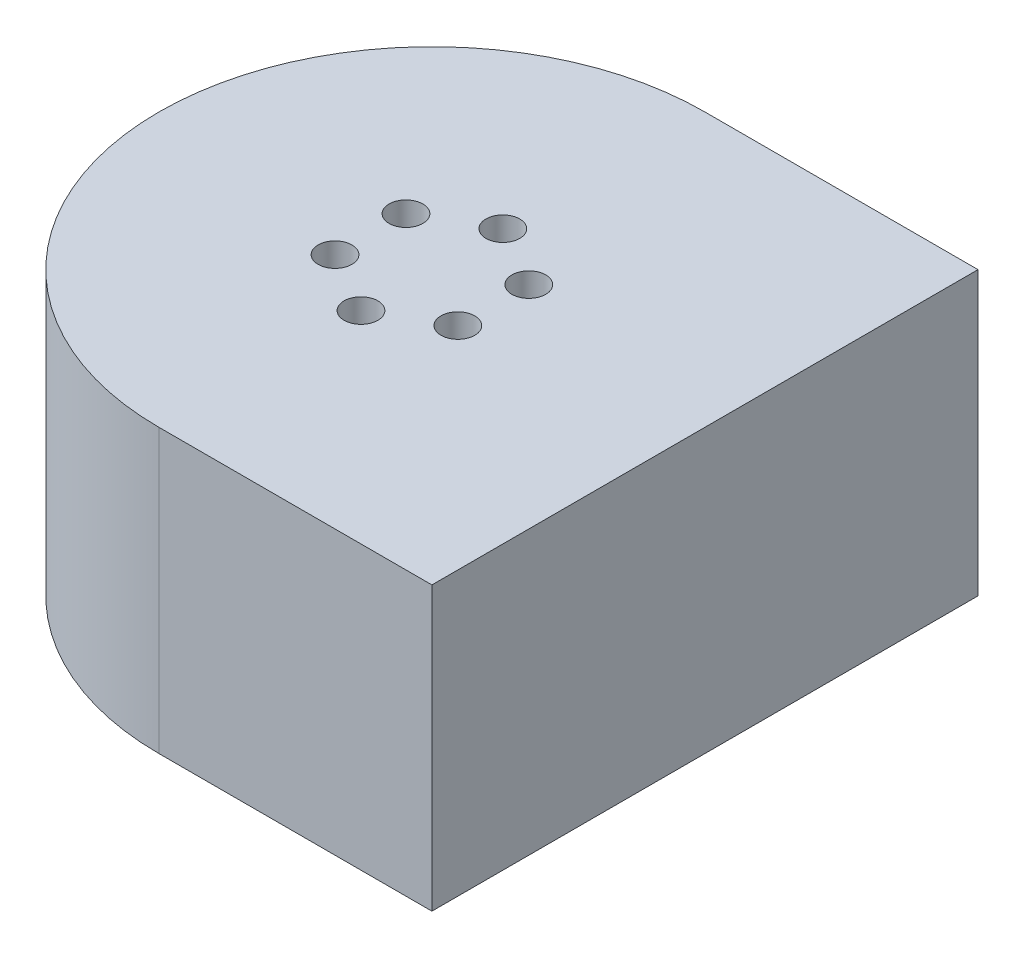
SolidWorks part; units mm, degrees
ref_plane "Front Plane" through (0, 0, 0) normal (0, 0, 1) x (1, 0, 0)
ref_plane "Top Plane" through (0, 0, 0) normal (0, 1, 0) x (1, 0, 0)
ref_plane "Right Plane" through (0, 0, 0) normal (1, 0, 0) x (0, 0, -1)
sketch "Sketch1" plane through (0, 0, 0) normal (0, 1, 0) x (1, 0, 0)
  line L0 (0, 44.45) -> (44.45, 44.45)
  line L1 (44.45, 44.45) -> (44.45, -44.45)
  line L2 (44.45, -44.45) -> (0, -44.45)
  arc A0 (0, 44.45) -> (0, -44.45) centre (0, 0) ccw
extrude "Boss-Extrude1" add sketch "Sketch1" along normal blind 46
sketch "Sketch2" plane through (0, 0, 0) normal (0, -1, 0) x (-1, 0, 0)
  line L1 (0, -11.547) -> (10, -5.7735)
  line L2 (10, -5.7735) -> (10, 5.7735)
  line L3 (10, 5.7735) -> (0, 11.547)
  line L4 (0, 11.547) -> (-10, 5.7735)
  line L5 (-10, 5.7735) -> (-10, -5.7735)
  line L6 (-10, -5.7735) -> (0, -11.547)
  circle A0 centre (0, 0) radius 10 construction
  circle A1 centre (0, -11.547) radius 2.75
  circle A2 centre (10, -5.7735) radius 2.75
  circle A3 centre (10, 5.7735) radius 2.75
  circle A4 centre (0, 11.547) radius 2.75
  circle A5 centre (-10, 5.7735) radius 2.75
  circle A6 centre (-10, -5.7735) radius 2.75
extrude "Cut-Extrude2" cut sketch "Sketch2" against normal blind 76 contours L6 A1 L1 | L5 A6 L6 | L4 A5 L5 | L3 A4 L4 | L2 A3 L3 | L1 A2 L2 | L2 A2 L1 | L1 A1 L6 | L6 A6 L5 | L5 A5 L4 | L4 A4 L3 | L3 A3 L2 region at (0, 0, 10.0309) region at (0, 0, 12.3051) region at (-8.687, 0, 5.0154) region at (-10.6565, 0, 6.1525) region at (10.6565, 0, 6.1525) region at (8.687, 0, 5.0154) region at (-8.687, 0, -5.0154) region at (-10.6565, 0, -6.1525) region at (10.6565, 0, -6.1525) region at (8.687, 0, -5.0154) region at (0, 0, -10.0309) region at (0, 0, -12.3051)
